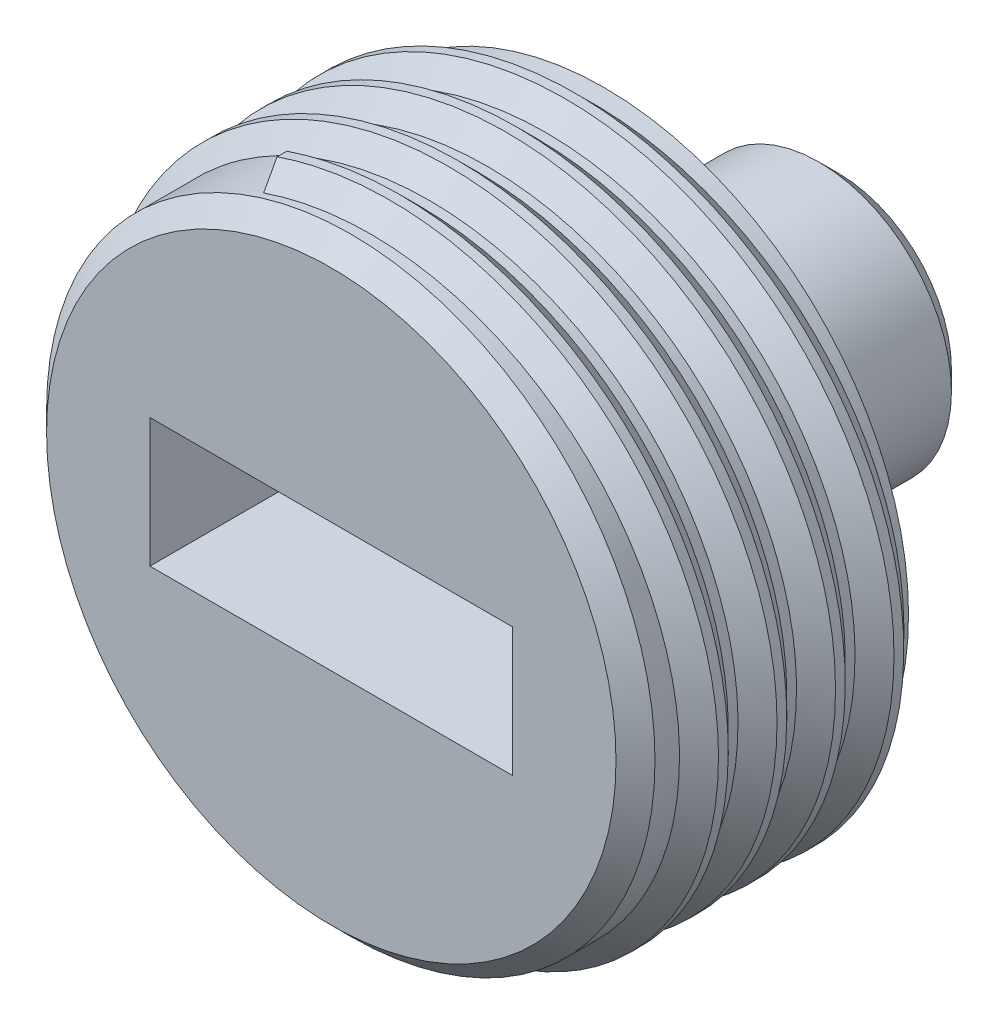
SolidWorks part; units mm, degrees
ref_plane "前视基准面" through (0, 0, 0) normal (0, 0, 1) x (1, 0, 0)
ref_plane "上视基准面" through (0, 0, 0) normal (0, 1, 0) x (1, 0, 0)
ref_plane "右视基准面" through (0, 0, 0) normal (1, 0, 0) x (0, 0, -1)
sketch "草图1" plane through (0, 0, 0) normal (0, 0, 1) x (1, 0, 0)
  circle A1 centre (0, 0) radius 15.6
  dimension "D1" = 31.2
extrude "凸台-拉伸1" add sketch "草图1" along normal blind 10
sketch "草图2" plane through (0, 0, 0) normal (0, 0, -1) x (-1, 0, 0)
  circle A0 centre (0, 0) radius 6.8
  dimension "D1" = 13.6
extrude "凸台-拉伸2" add sketch "草图2" along normal blind 12
sketch "草图6" plane through (0, 0, 0) normal (0, 0, -1) x (-1, 0, 0)
  circle A0 centre (0, 0) radius 6.8 construction
  circle A1 centre (0, 0) radius 6.8
  circle A2 centre (0, 0) radius 19.1268
sketch "草图7" plane through (0, 0, 10) normal (0, 0, 1) x (1, 0, 0)
  circle A0 centre (0, 0) radius 15.6
  dimension "D3" = 31.2
extrude "凸台-拉伸3" add sketch "草图7" along normal blind 4
sketch "草图8" plane through (0, 0, 14) normal (0, 0, 1) x (1, 0, 0)
  line L1 (-9.3, -3.3) -> (9.3, -3.3)
  line L2 (-9.3, -3.3) -> (-9.3, 3.3)
  line L3 (-9.3, 3.3) -> (9.3, 3.3)
  line L4 (9.3, -3.3) -> (9.3, 3.3)
  line L5 (-9.3, -3.3) -> (9.3, 3.3) construction
  line L6 (-9.3, 3.3) -> (9.3, -3.3) construction
  point P0 (0, 0)
  dimension "D1" = 6.6
  dimension "D2" = 18.6
extrude "切除-拉伸3" cut sketch "草图8" against normal blind 10
fillet "圆角1" radius 1 2 edges at (-6.8, 0, -12) (15.6, 0, 14) profile chamfer
chamfer "倒角1" distance 3.2 angle 45 2 edges at (0, 3.3, 4) (0, -3.3, 4)
sketch "草图10" plane through (0, 0, 0) normal (0, 0, -1) x (-1, 0, 0)
  circle A0 centre (0, 0) radius 15.6 construction
  circle A1 centre (0, 0) radius 15.6
curve "螺旋线/涡状线1" pitch 3 height 11.4 radius 15.6 centre (0, 0, 0) axis (0, 0, 1) start towards (-1, 0, 0)
sketch "草图12" plane through (0, 0, 0) normal (0, 1, 0) x (1, 0, 0)
  line L0 (-15.6, 1.25) -> (-15.6, -1.25)
  line L4 (-16.6, 0.25) -> (-15.6, 1.25)
  line L5 (-16.6, -0.25) -> (-16.6, 0.25)
  line L6 (-15.6, -1.25) -> (-16.6, -0.25)
  point P4 (-15.6, 0)
  dimension "D3" = 2.5
sweep "扫描1" add profiles "草图12" path "螺旋线/涡状线1"
extrude "切除-拉伸4" cut sketch "草图6" along normal blind 10
